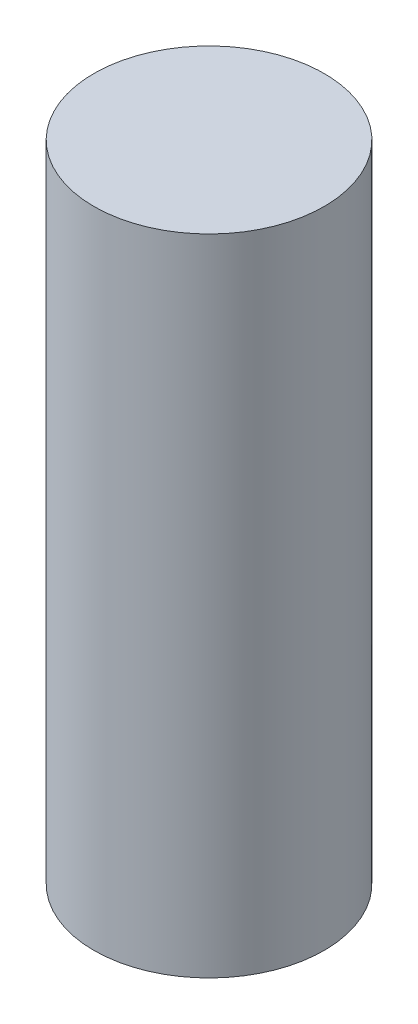
SolidWorks part; units mm, degrees
ref_plane "Front Plane" through (0, 0, 0) normal (0, 0, 1) x (1, 0, 0)
ref_plane "Top Plane" through (0, 0, 0) normal (0, 1, 0) x (1, 0, 0)
ref_plane "Right Plane" through (0, 0, 0) normal (1, 0, 0) x (0, 0, -1)
sketch "Sketch1" plane through (0, 0, 0) normal (0, 1, 0) x (1, 0, 0)
  circle A0 centre (0, 0) radius 7.15
extrude "Boss-Extrude1" add sketch "Sketch1" along normal blind 40
